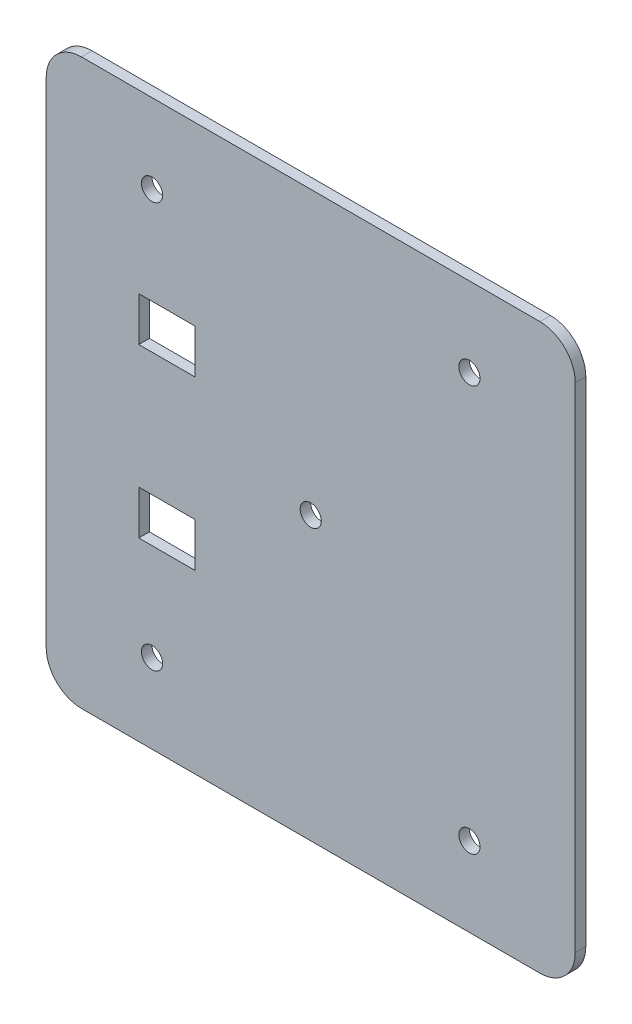
SolidWorks part; units mm, degrees
ref_plane "Front Plane" through (0, 0, 0) normal (0, 0, 1) x (1, 0, 0)
ref_plane "Top Plane" through (0, 0, 0) normal (0, 1, 0) x (1, 0, 0)
ref_plane "Right Plane" through (0, 0, 0) normal (1, 0, 0) x (0, 0, -1)
sketch "Sketch1" plane through (0, 0, 0) normal (0, 0, 1) x (1, 0, 0)
  line L0 (-22.5, -22.5) -> (22.5, -22.5) construction
  line L1 (22.5, -22.5) -> (22.5, 22.5) construction
  line L2 (22.5, 22.5) -> (-22.5, 22.5) construction
  line L3 (-22.5, 22.5) -> (-22.5, -22.5) construction
  line L4 (22.5, 92.5) -> (22.5, 137.5) construction
  line L5 (22.5, 137.5) -> (-22.5, 137.5) construction
  line L6 (-22.5, 137.5) -> (-22.5, 92.5) construction
  line L7 (-22.5, 92.5) -> (22.5, 92.5) construction
  line L8 (-22.5, -22.5) -> (22.5, -22.5)
  line L9 (22.5, -22.5) -> (22.5, 22.5)
  line L10 (22.5, 22.5) -> (-22.5, 22.5)
  line L11 (-22.5, 22.5) -> (-22.5, -22.5)
  line L12 (22.5, 92.5) -> (22.5, 137.5)
  line L13 (22.5, 137.5) -> (-22.5, 137.5)
  line L14 (-22.5, 137.5) -> (-22.5, 92.5)
  line L15 (-22.5, 92.5) -> (22.5, 92.5)
  line L16 (-22.5, 92.5) -> (22.5, 137.5)
  line L17 (-22.5, 137.5) -> (22.5, 92.5)
  line L18 (22.5, 22.5) -> (-22.5, -22.5)
  line L19 (-22.5, 22.5) -> (22.5, -22.5)
  line L20 (75, -102.5) -> (75, 57.5)
  line L21 (-55, -102.5) -> (75, -102.5)
  line L22 (-75, -82.5) -> (-75, 197.5)
  line L23 (75, -102.5) -> (75, 217.5)
  line L24 (-55, 217.5) -> (75, 217.5)
  line L25 (-75, -102.5) -> (75, 217.5) construction
  line L26 (75, -102.5) -> (-75, 217.5) construction
  line L27 (0, 0) -> (0, 57.5)
  line L28 (75, -102.5) -> (75, 217.5)
  line L29 (75, -102.5) -> (205, -102.5)
  line L30 (75, 217.5) -> (205, 217.5)
  line L31 (225, -82.5) -> (225, 197.5)
  line L32 (165, 217.5) -> (165, 172.5)
  line L33 (165, 172.5) -> (225, 172.5)
  line L34 (225, -57.5) -> (165, -57.5)
  line L35 (165, -57.5) -> (165, -102.5)
  line L36 (-15, -102.5) -> (-15, -57.5)
  line L37 (-15, -57.5) -> (-75, -57.5)
  line L38 (-75, 172.5) -> (-15, 172.5)
  line L39 (-15, 172.5) -> (-15, 217.5)
  line L40 (-22.5, 92.5) -> (9.5, 92.5)
  line L41 (-22.5, 92.5) -> (-22.5, 117.5)
  line L42 (9.5, 92.5) -> (9.5, 117.5)
  line L43 (-22.5, 117.5) -> (9.5, 117.5)
  line L44 (-22.5, 22.5) -> (9.5, 22.5)
  line L45 (-22.5, 22.5) -> (-22.5, -2.5)
  line L46 (9.5, 22.5) -> (9.5, -2.5)
  line L47 (-22.5, -2.5) -> (9.5, -2.5)
  circle A0 centre (-15, 172.5) radius 6
  circle A1 centre (165, 172.5) radius 6
  circle A2 centre (165, -57.5) radius 6
  circle A3 centre (-15, -57.5) radius 6
  circle A4 centre (75, 57.5) radius 6
  arc A5 (-75, -82.5) -> (-55, -102.5) centre (-55, -82.5) ccw
  arc A6 (205, -102.5) -> (225, -82.5) centre (205, -82.5) ccw
  arc A7 (205, 217.5) -> (225, 197.5) centre (205, 197.5) cw
  arc A8 (-75, 197.5) -> (-55, 217.5) centre (-55, 197.5) cw
  point P7 (0, 57.5)
  point P43 (225, 217.5)
  dimension "D7" = 12
  dimension "D8" = 160
  dimension "D9" = 20
  dimension "D1" = 150
  dimension "D2" = 320
  dimension "D3" = 57.5
  dimension "D4" = 150
  dimension "D5" = 60
  dimension "D6" = 45
  dimension "D10" = 45
  dimension "D11" = 25
  dimension "D12" = 25
  dimension "D13" = 32
extrude "Boss-Extrude1" add sketch "Sketch1" along normal blind 6 contours L22 A5 L21 L36 A3 L37 | A4 L28 L24 L39 A0 L38 L22 L37 A3 L36 L21 L20 L15 L14 L13 L12 L11 L10 L9 L8 | A4 L20 L29 L35 A2 L34 L31 L33 A1 L32 L30 L28 | L29 A6 L31 L34 A2 L35 | A7 L30 L32 A1 L33 L31 | A8 L22 L38 A0 L39 L24 | L16 L43 L42 L17 L12 | L42 L15 L17 | L17 L43 L16 L13 | L14 L43 L17 | L47 L18 L8 L19 | L47 L19 L9 L18 L46 | L10 L46 L18 | L47 L11 L18 region at (0, -15.1667, 0) region at (-15.8333, -9.1667, 0) region at (16.34, -0.2688, 0) region at (13.8333, 18.1667, 0) region at (16.34, 115.2688, 0) region at (13.8333, 96.8333, 0) region at (0, 130.1667, 0) region at (-15.8333, 124.1667, 0) region at (6.2964, 57.5, 0) region at (144.3054, 57.5, 0) region at (-44.4526, -79.6196, 0) region at (194.4526, -79.6196, 0) region at (-44.4526, 194.6196, 0) region at (194.4526, 194.6196, 0)
